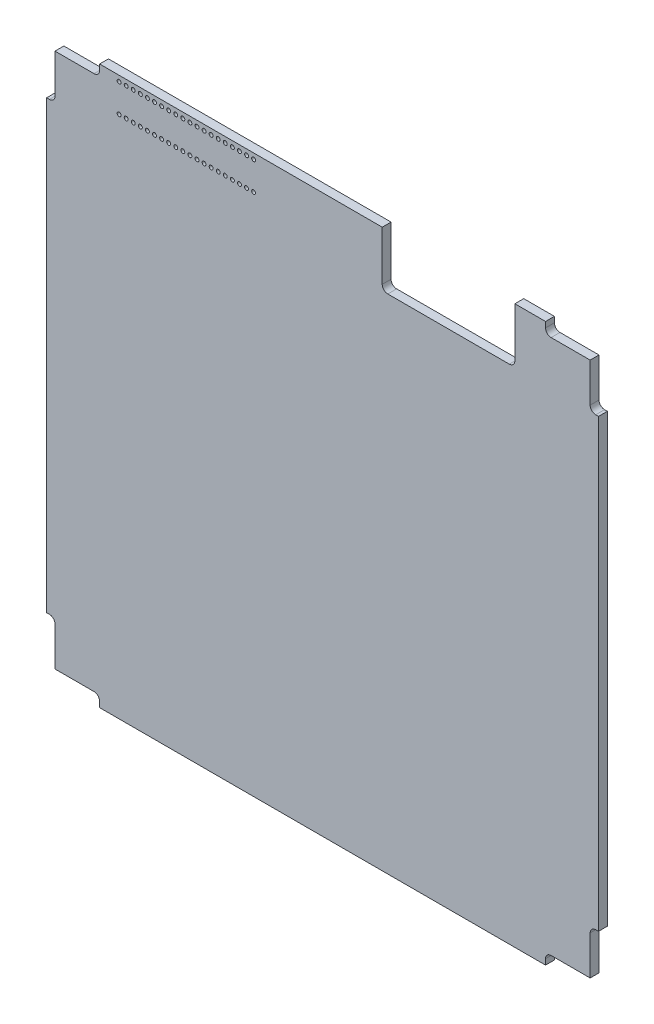
SolidWorks part; units mm, degrees
material "ABS"
ref_plane "Front Plane" through (0, 0, 0) normal (0, 0, 1) x (1, 0, 0)
ref_plane "Top Plane" through (0, 0, 0) normal (0, 1, 0) x (1, 0, 0)
ref_plane "Right Plane" through (0, 0, 0) normal (1, 0, 0) x (0, 0, -1)
sketch "Sketch1" plane through (0, 0, 0) normal (0, 0, 1) x (1, 0, 0)
  line L0 (-40, 50) -> (-40, 48)
  line L1 (-50, -50) -> (50, -50)
  line L2 (-50, -50) -> (-50, 50)
  line L3 (-50, 50) -> (50, 50)
  line L4 (50, -50) -> (50, 50)
  line L5 (-50, -50) -> (50, 50) construction
  line L6 (-50, 50) -> (50, -50) construction
  line L7 (-50, 50) -> (-40, 50)
  line L8 (-50, 50) -> (-50, 40)
  line L9 (-40, 48) -> (-48, 48)
  line L10 (-48, 48) -> (-48, 40)
  line L11 (50, 50) -> (40, 50)
  line L12 (50, 50) -> (50, 40)
  line L13 (-48, 40) -> (-50, 40)
  line L14 (50, 40) -> (48, 40)
  line L15 (-50, -50) -> (-37.8649, -50)
  line L16 (-50, -50) -> (-50, -37.8649)
  line L17 (50, 50) -> (50, 40)
  line L18 (50, 50) -> (40, 50)
  line L19 (50, -50) -> (41.5, -50)
  line L20 (50, -50) -> (50, -41.5)
  line L21 (48, 40) -> (48, 48)
  line L22 (48, 48) -> (40, 48)
  line L23 (40, 48) -> (40, 50)
  line L24 (40, -50) -> (40, -48)
  line L25 (50, -50) -> (40, -50)
  line L26 (50, -50) -> (50, -40)
  line L27 (40, -48) -> (48, -48)
  line L28 (48, -48) -> (48, -40)
  line L29 (48, -40) -> (50, -40)
  line L30 (-50, -40) -> (-48, -40)
  line L31 (-50, -50) -> (-50, -40)
  line L32 (-50, -50) -> (-40, -50)
  line L33 (-48, -40) -> (-48, -48)
  line L34 (-48, -48) -> (-40, -48)
  line L35 (-40, -48) -> (-40, -50)
  point P0 (0, 0)
  point P38 (0, 0)
  dimension "D1" = 100
  dimension "D2" = 100
  dimension "D3" = 2
  dimension "D4" = 10
  dimension "D5" = 4
extrude "Boss-Extrude1" add sketch "Sketch1" along normal blind 1.5875 contours L1 L4 L3 L2 region at (0, 0, 0)
fillet "Fillet1" radius 1 8 edges at (-48, -40, 0.7937) (-40, -48, 0.7937) (40, -48, 0.7937) (48, -40, 0.7937) (48, 40, 0.7937) (40, 48, 0.7937) (-40, 48, 0.7937) (-48, 40, 0.7937)
sketch "Sketch2" plane through (0, 0, 1.5875) normal (0, 0, 1) x (1, 0, 0)
  line L0 (0, 50) -> (0, -50) construction
  line L1 (-40, 50) -> (40, 50) construction
  line L2 (-40, -50) -> (40, -50) construction
  line L3 (-50, -40) -> (-50, 40) construction
  line L4 (-40, 50) -> (40, 50) construction
  circle A0 centre (-36.5, 49) radius 0.35
  circle A1 centre (-35.23, 49) radius 0.35
  circle A2 centre (-33.96, 49) radius 0.35
  circle A3 centre (-32.69, 49) radius 0.35
  circle A4 centre (-31.42, 49) radius 0.35
  circle A5 centre (-30.15, 49) radius 0.35
  circle A6 centre (-28.88, 49) radius 0.35
  circle A7 centre (-27.61, 49) radius 0.35
  circle A8 centre (-26.34, 49) radius 0.35
  circle A9 centre (-25.07, 49) radius 0.35
  circle A10 centre (-23.8, 49) radius 0.35
  circle A11 centre (-22.53, 49) radius 0.35
  circle A12 centre (-21.26, 49) radius 0.35
  circle A13 centre (-19.99, 49) radius 0.35
  circle A14 centre (-18.72, 49) radius 0.35
  circle A15 centre (-17.45, 49) radius 0.35
  circle A16 centre (-16.18, 49) radius 0.35
  circle A17 centre (-14.91, 49) radius 0.35
  circle A18 centre (-13.64, 49) radius 0.35
  circle A19 centre (-12.37, 49) radius 0.35
  circle A20 centre (-35.23, 43.92) radius 0.35
  circle A21 centre (-33.96, 43.92) radius 0.35
  circle A22 centre (-32.69, 43.92) radius 0.35
  circle A23 centre (-31.42, 43.92) radius 0.35
  circle A24 centre (-30.15, 43.92) radius 0.35
  circle A25 centre (-28.88, 43.92) radius 0.35
  circle A26 centre (-27.61, 43.92) radius 0.35
  circle A27 centre (-26.34, 43.92) radius 0.35
  circle A28 centre (-25.07, 43.92) radius 0.35
  circle A29 centre (-23.8, 43.92) radius 0.35
  circle A30 centre (-22.53, 43.92) radius 0.35
  circle A31 centre (-21.26, 43.92) radius 0.35
  circle A32 centre (-19.99, 43.92) radius 0.35
  circle A33 centre (-18.72, 43.92) radius 0.35
  circle A34 centre (-17.45, 43.92) radius 0.35
  circle A35 centre (-16.18, 43.92) radius 0.35
  circle A36 centre (-14.91, 43.92) radius 0.35
  circle A37 centre (-13.64, 43.92) radius 0.35
  circle A38 centre (-12.37, 43.92) radius 0.35
  circle A39 centre (-36.5, 43.92) radius 0.35
  dimension "D1" = 0.7
  dimension "D4" = 13.5
  dimension "D5" = 1
  dimension "D2" = 5.08
  dimension "D3" = 1.27
extrude "Cut-Extrude1" cut sketch "Sketch2" against normal through all
sketch "Sketch3" plane through (0, 50, 0) normal (0, 1, 0) x (1, 0, 0)
  line L0 (-40, 0) -> (40, 0) construction
  line L1 (10.7, 0) -> (19.7, 0)
  line L2 (10.7, 0) -> (10.7, -1.5875)
  line L3 (10.7, -1.5875) -> (19.7, -1.5875)
  line L4 (-40, -1.5875) -> (-40, 0) construction
  line L5 (-40, -1.5875) -> (40, -1.5875) construction
  line L6 (15.2, 0) -> (15.2, -1.5875) construction
  line L7 (12, 0) -> (12, -1.5875) construction
  line L8 (18.4, 0) -> (18.4, -1.5875) construction
  line L9 (-40, -1.5875) -> (40, -1.5875) construction
  line L12 (19.7, 0) -> (34.5, 0)
  line L14 (19.7, -1.5875) -> (34.5, -1.5875)
  line L15 (34.5, 0) -> (34.5, -1.5875)
  dimension "D1" = 9
  dimension "D2" = 6.4
  dimension "D3" = 3.2
  dimension "D5" = 14.8
  dimension "D6" = 50.7
extrude "Cut-Extrude2" cut sketch "Sketch3" against normal blind 9.8806
fillet "Fillet2" radius 1 2 edges at (10.7, 40.1194, 0.7938) (34.5, 40.1194, 0.7937)
sketch "Sketch5" plane through (0, 0, 0) normal (0, 0, -1) x (-1, 0, 0)
  line L0 (40, -50) -> (-40, -50) construction
  line L1 (-49.5, 50) -> (49.5, 50)
  line L2 (-49.5, 50) -> (-49.5, -50)
  line L3 (-49.5, -50) -> (49.5, -50)
  line L4 (49.5, 50) -> (49.5, -50)
  line L5 (40, 50) -> (-10.7, 50) construction
  line L6 (50, -40) -> (50, 40) construction
  dimension "D1" = 99
  dimension "D2" = 0.5
extrude "Cut-Extrude3" cut sketch "Sketch5" against normal through all flip side to cut
